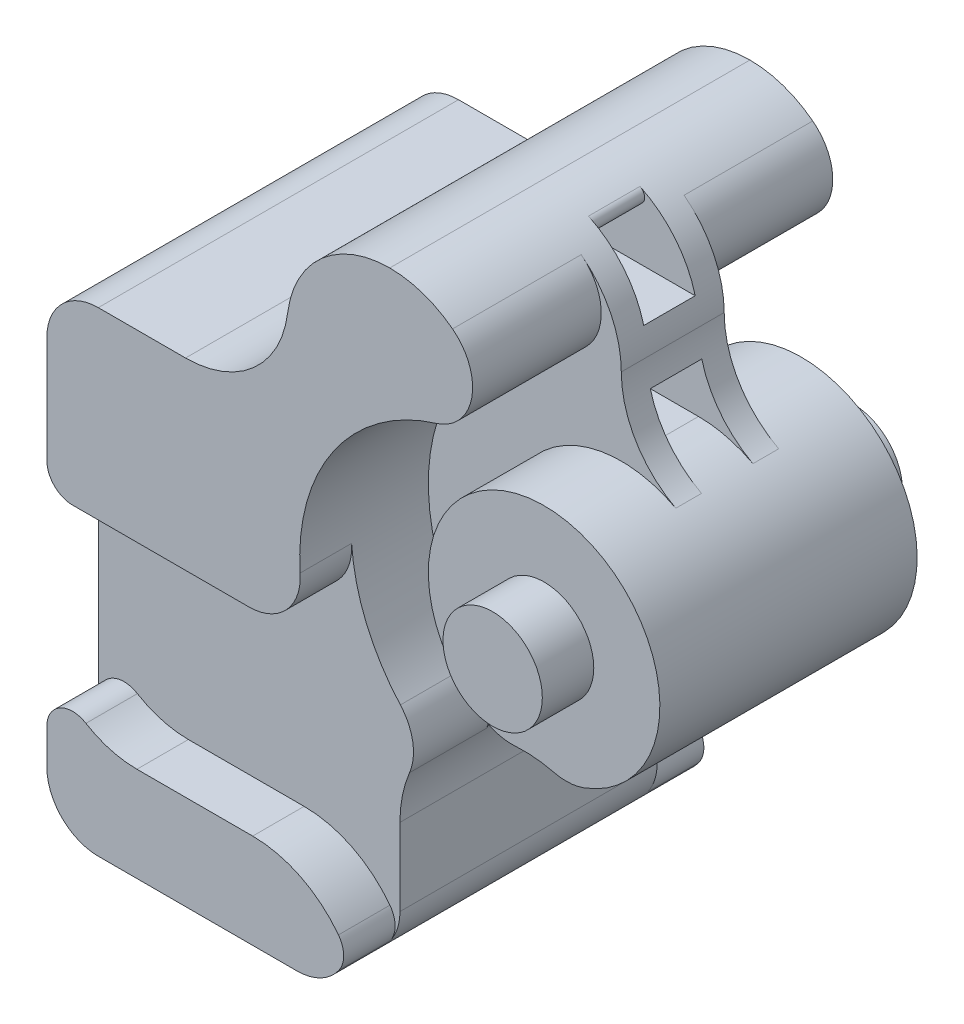
SolidWorks part; units mm, degrees
material "ABS"
ref_plane "Front Plane" through (0, 0, 0) normal (0, 0, 1) x (1, 0, 0)
ref_plane "Top Plane" through (0, 0, 0) normal (0, 1, 0) x (1, 0, 0)
ref_plane "Right Plane" through (0, 0, 0) normal (1, 0, 0) x (0, 0, -1)
sketch "Sketch1" plane through (0, 0, 0) normal (0, 0, 1) x (1, 0, 0)
  line L0 (5.5562, 0) -> (16.6687, 0)
  line L1 (0, 5.5562) -> (22.225, 5.5562)
  line L4 (22.225, 5.5562) -> (22.225, -5.5562) construction
  line L5 (0, 5.5562) -> (22.225, 5.5562) construction
  line L9 (13.1316, 0.7956) -> (22.225, 0) construction
  line L10 (22.225, 0) -> (22.225, -9.1281) construction
  line L11 (5.5562, 0) -> (0, 0)
  line L12 (0, 0) -> (0, 5.5562)
  line L13 (13.7542, 7.9121) -> (13.1316, 0.7956) construction
  circle A0 centre (0, 0) radius 5.5562 construction
  circle A1 centre (22.225, 0) radius 5.5562 construction
  circle A2 centre (22.225, -9.1281) radius 3.5719
  arc A3 (22.225, -5.5562) -> (22.225, 5.5562) centre (22.225, 0) ccw
  circle A5 centre (22.225, 0) radius 1.7859
  circle A6 centre (22.225, -9.1281) radius 1.7859
  arc A7 (16.6687, 0) -> (22.225, -5.5562) centre (22.225, 0) ccw
  circle A23 centre (22.225, 0) radius 9.1281 construction
  circle A30 centre (2.7781, 2.7781) radius 2.7781
  circle A31 centre (0.8137, 4.7426) radius 0.8137
  circle A32 centre (13.1316, 0.7956) radius 1.7859
  circle A33 centre (13.1316, 0.7956) radius 3.5719
  circle A34 centre (13.7542, 7.9121) radius 1.7859
  circle A35 centre (13.7542, 7.9121) radius 3.5719
  arc A36 (14.9108, 0.6399) -> (22.225, -7.3422) centre (22.225, 0) ccw
  arc A37 (22.225, -10.9141) -> (11.3525, 0.9512) centre (22.225, 0) cw
  arc A38 (22.225, -12.7) -> (9.5733, 1.1069) centre (22.225, 0) cw
  dimension "D1" = 22.225
  dimension "D2" = 11.1125
  dimension "D3" = 3.5719
  dimension "D5" = 7.1437
  dimension "D4" = 95
sketch "Sketch3" plane through (0, 0, 0) normal (0, 0, 1) x (1, 0, 0)
  line L0 (0.8137, 5.5562) -> (11.0694, 5.5562)
  line L1 (0, 5.5562) -> (22.225, 5.5562) construction
  line L2 (0, 5.5562) -> (0, 2.7781)
  line L3 (2.7781, 0) -> (9.6495, 0)
  line L4 (5.5562, 0) -> (16.6687, 0) construction
  line L5 (0, 2.7781) -> (0, 0)
  line L6 (0, 0) -> (2.7781, 0)
  line L7 (0, 0) -> (0, -3.175)
  line L8 (0, -3.175) -> (9.6495, -3.175)
  line L9 (9.6495, -3.175) -> (9.6495, 0)
  line L10 (0, 5.5562) -> (0.8137, 5.5562)
  line L11 (0, 5.5562) -> (0, 11.484)
  line L12 (0, 11.484) -> (13.7542, 11.484)
  line L13 (9.3057, 0.7956) -> (9.3057, -3.175)
  circle A0 centre (13.1316, 0.7956) radius 3.5719
  circle A1 centre (13.7542, 7.9121) radius 3.5719
  circle A2 centre (13.7542, 7.9121) radius 1.5319
  circle A3 centre (13.1316, 0.7956) radius 3.5719 construction
  circle A5 centre (13.7542, 7.9121) radius 3.5719 construction
  circle A6 centre (0.8137, 4.7426) radius 0.8137 construction
  circle A8 centre (2.7781, 2.7781) radius 2.7781
  circle A9 centre (13.1316, 0.7956) radius 3.8259
  arc A11 (9.5733, 1.1069) -> (9.6495, -1.7736) centre (22.225, 0) ccw
  point P40 (9.3057, -3.175)
  dimension "D2" = 3.0639
  dimension "D3" = 0.254
  dimension "D1" = 3.175
extrude "Boss-Extrude1" add sketch "Sketch3" along normal blind 7.9375 contours A8 L3 A0 A1 L0 | A1 A2 | A8 | A8 L2 | A8 | A8 | A8 L0 | A8 L5 L6 | L8 L9 L3 L6 L7 | A1 L12 L11 L10 L0 region at (5.3993, 8.5885, 0) region at (0.6205, 4.9357, 0) region at (7.663, 3.0491, 0) region at (2.7781, 2.7781, 0) region at (10.5922, 9.3443, 0) region at (0.6205, 0.6205, 0) region at (4.6529, -1.5875, 0)
extrude "Boss-Extrude2" add sketch "Sketch3<4>" along normal blind 9.525 and the other way blind 1.5875 contours A2 region at (13.7542, 7.9121, 0)
sketch "Sketch3<4>" plane through (0, 0, 0) normal (0, 0, 1) x (1, 0, 0) same geometry as "Sketch3"
sketch "Sketch7" plane through (0, 0, 7.9375) normal (0, 0, 1) x (1, 0, 0)
  line L0 (0, 5.5562) -> (11.1125, 5.5562)
  line L1 (0, 5.5562) -> (22.225, 5.5562) construction
  line L2 (0, 0) -> (9.525, 0)
  line L3 (5.5562, 0) -> (16.6687, 0) construction
  line L4 (22.225, 5.5562) -> (22.225, -5.5562) construction
  line L5 (0, 0) -> (0, -3.175)
  line L6 (0, -3.175) -> (9.3057, -3.175)
  line L9 (13.7542, 11.484) -> (0, 11.484)
  line L10 (0, 11.484) -> (0, 5.5562)
  line L13 (9.3057, 0) -> (9.3057, -3.175)
  line L14 (9.3057, 0.7956) -> (9.3057, -3.175) construction
  arc A0 (9.5733, 1.1069) -> (22.225, -12.7) centre (22.225, 0) ccw construction
  circle A1 centre (22.225, 0) radius 12.7
  circle A2 centre (13.7542, 7.9121) radius 3.5719
  circle A3 centre (13.7542, 7.9121) radius 3.5719 construction
  circle A4 centre (2.7781, 2.7781) radius 2.7781
  circle A5 centre (2.7781, 2.7781) radius 2.7781 construction
  circle A6 centre (0.8137, 4.7426) radius 0.8137
  circle A7 centre (0.8137, 4.7426) radius 0.8137 construction
  line M3 (0, 11.484) -> (0, -3.175)
  line M4 (0, -3.175) -> (9.3057, -3.175)
  line M8 (13.7542, 11.484) -> (0, 11.484)
extrude "Boss-Extrude3" add sketch "Sketch7" along normal blind 1.5875 contours A2 L0 A1 M8 M3 | A2 A1 L0 | A1 L2 M3 M4 | A6 L0 M3 | A4 L2 M3 region at (5.397, 8.5897, 7.9375) region at (0.1818, 5.3745, 7.9375) region at (0.6205, 0.6205, 7.9375) region at (10.9254, 5.623, 7.9375) region at (4.6529, -1.5875, 7.9375)
extrude "Boss-Extrude4" add sketch "Sketch7<3>" against normal blind 1.5875 from surface contours L2 M3 M4 | A2 L0 A1 M8 M3 | A6 L0 M3 | A4 L2 M3 | A2 A1 L0 region at (5.397, 8.5897, 7.9375) region at (0.1818, 5.3745, 7.9375) region at (0.6205, 0.6205, 7.9375) region at (10.9254, 5.623, 7.9375) region at (4.6529, -1.5875, 7.9375) starting at face at (8.1785, 3.9061, 0)
sketch "Sketch7<3>" plane through (0, 0, 7.9375) normal (0, 0, 1) x (1, 0, 0) same geometry as "Sketch7"
fillet "Fillet1" radius 3.5719 2 edges at (11.0694, 5.5562, -0.7937) (11.0694, 5.5562, 8.7312)
sketch "Sketch8" plane through (0, 0, 9.525) normal (0, 0, 1) x (1, 0, 0)
  line L4 (9.3057, -3.175) -> (9.3057, 0)
  line L5 (0, 2.7781) -> (0, -3.175)
  line L6 (0, -3.175) -> (9.3057, -3.175)
  line L7 (9.3057, -3.175) -> (9.3057, 0)
  line L9 (0, 2.7781) -> (0, -3.175)
  line L10 (0, -3.175) -> (9.3057, -3.175)
  line L13 (9.3057, 0) -> (2.7781, 0)
  line L14 (9.3057, 0) -> (2.7781, 0)
  circle A0 centre (6.35, -3.5719) radius 3.5719
  arc A2 (0, 2.7781) -> (2.7781, 0) centre (2.7781, 2.7781) ccw
  arc A3 (0, 2.7781) -> (2.7781, 0) centre (2.7781, 2.7781) ccw
  point P2 (6.35, 0)
  dimension "D2" = 7.1437
  dimension "D1" = 3.5719
  dimension "D3" = 0
extrude "Cut-Extrude5" cut sketch "Sketch8" against normal blind 1.5875 contours A0 region at (8.6031, -0.4448, 9.525)
extrude "Cut-Extrude6" cut sketch "Sketch8<4>" against normal blind 1.5875 from surface contours A0 region at (8.6031, -0.4448, 9.525) starting at face at (15.2862, 7.9121, 0)
sketch "Sketch8<4>" plane through (0, 0, 9.525) normal (0, 0, 1) x (1, 0, 0) same geometry as "Sketch8"
sketch "Sketch9" plane through (0, 0, 9.525) normal (0, 0, 1) x (1, 0, 0)
  line L0 (0.8137, 5.8102) -> (6.7147, 5.8102)
  line L1 (11.8492, 11.23) -> (0.254, 11.23)
  line L2 (0.254, 11.23) -> (0.254, 5.6518)
  line L3 (0.8137, 5.5562) -> (6.7147, 5.5562)
  line L4 (13.7542, 11.484) -> (0, 11.484)
  line L5 (0, 11.484) -> (0, 4.7426)
  line L6 (0.8137, 5.5562) -> (6.7147, 5.5562)
  line L7 (13.7542, 11.484) -> (0, 11.484)
  line L8 (0, 11.484) -> (0, 4.7426)
  line L9 (9.0517, -2.921) -> (9.0517, -1.646)
  line L10 (9.3057, -3.175) -> (9.3057, -1.5664)
  line L11 (6.35, 0) -> (2.7781, 0)
  line L12 (0, 2.7781) -> (0, -3.175)
  line L13 (0, -3.175) -> (9.3057, -3.175)
  line L16 (0, 2.7781) -> (0, -3.175)
  line L17 (0, -3.175) -> (9.3057, -3.175)
  line L18 (6.35, -0.254) -> (2.7781, -0.254)
  line L19 (0.254, 1.0981) -> (0.254, -2.921)
  line L20 (0.254, -2.921) -> (9.0517, -2.921)
  line L25 (6.35, 0) -> (2.7781, 0) construction
  line L26 (6.35, 0) -> (2.7781, 0)
  line L27 (9.3057, -3.175) -> (9.3057, -1.5664) construction
  line L28 (9.3057, -3.175) -> (9.3057, -1.5664)
  arc A0 (6.7147, 5.8102) -> (9.051, 11.484) centre (6.7147, 9.1281) ccw
  arc A1 (12.3835, 11.484) -> (9.9842, 8.5634) centre (13.7542, 7.9121) ccw
  arc A2 (9.3057, -1.5664) -> (6.35, 0) centre (6.35, -3.5719) ccw
  arc A3 (6.7147, 5.5562) -> (10.2345, 8.5201) centre (6.7147, 9.1281) ccw
  arc A4 (13.7542, 11.484) -> (10.2345, 8.5201) centre (13.7542, 7.9121) ccw
  arc A5 (0.8137, 5.5562) -> (0, 4.7426) centre (0.8137, 4.7426) ccw
  arc A6 (6.7147, 5.5562) -> (10.2345, 8.5201) centre (6.7147, 9.1281) ccw
  arc A7 (13.7542, 11.484) -> (10.2345, 8.5201) centre (13.7542, 7.9121) ccw
  arc A8 (0.8137, 5.5562) -> (0, 4.7426) centre (0.8137, 4.7426) ccw
  arc A9 (0, 2.7781) -> (2.7781, 0) centre (2.7781, 2.7781) ccw
  arc A10 (9.3057, -1.5664) -> (6.35, 0) centre (6.35, -3.5719) ccw
  arc A11 (0, 2.7781) -> (2.7781, 0) centre (2.7781, 2.7781) ccw
  arc A12 (0.8137, 5.8102) -> (0, 5.4338) centre (0.8137, 4.7426) ccw
  arc A13 (9.6441, -3.175) -> (6.35, -0.254) centre (6.35, -3.5719) ccw
  arc A14 (0, 1.5633) -> (2.7781, -0.254) centre (2.7781, 2.7781) ccw
  arc A15 (0.8137, 5.8102) -> (0.254, 5.6518) centre (0.8137, 4.7426) ccw construction
  arc A16 (6.7147, 5.8102) -> (9.9842, 8.5634) centre (6.7147, 9.1281) ccw construction
  arc A17 (0.254, 1.0981) -> (2.7781, -0.254) centre (2.7781, 2.7781) ccw construction
  arc A18 (9.0517, -1.646) -> (6.35, -0.254) centre (6.35, -3.5719) ccw construction
  arc A19 (11.8492, 11.23) -> (9.9842, 8.5634) centre (13.7542, 7.9121) ccw construction
  line M19 (0.8137, 5.5562) -> (6.7147, 5.5562)
  arc M20 (6.7147, 5.5562) -> (10.2345, 8.5201) centre (6.7147, 9.1281) ccw
  arc M21 (10.2345, 8.5201) -> (13.7542, 11.484) centre (13.7542, 7.9121) cw
  line M22 (13.7542, 11.484) -> (0, 11.484)
  arc M24 (0, 4.7426) -> (0.8137, 5.5562) centre (0.8137, 4.7426) cw
  dimension "D1" = 0
  dimension "D2" = 0
  dimension "D3" = 0.254
  dimension "D4" = 0.254
extrude "Cut-Extrude7" cut sketch "Sketch9" against normal blind 1.5875 contours L0 A12 L8 A0 M24 M19 M20 M21 M22 | L16 A14 L18 A13 L17 A10 A11 region at (3.7642, 5.6571, 9.525) region at (4.5043, -0.0587, 9.525)
extrude "Cut-Extrude8" cut sketch "Sketch9<3>" against normal blind 1.5875 from surface contours L16 A14 L18 A13 L17 A10 A11 | L0 A12 L8 A0 M24 M19 M20 M21 M22 region at (3.7642, 5.6571, 9.525) region at (4.5043, -0.0587, 9.525) starting at face at (15.2862, 7.9121, 0)
sketch "Sketch9<3>" plane through (0, 0, 9.525) normal (0, 0, 1) x (1, 0, 0) same geometry as "Sketch9"
fillet "Fillet3" radius 1.5875 3 edges at (0, -3.175, 3.9688) (0, 11.484, 3.9688) (9.3057, -3.175, 3.9688)
fillet "Fillet2" radius 0.7937 8 edges at (0, 5.4338, -0.7937) (0, 1.5633, -0.7937) (0, 1.5633, 8.7312) (0, 5.4338, 8.7312) (12.3835, 11.484, 8.7312) (12.3835, 11.484, -0.7937) (9.2579, -1.9743, -0.7938) (9.2579, -1.9743, 8.7312)
sketch "Sketch10" plane through (0, 0, 9.525) normal (0, 0, 1) x (1, 0, 0)
  line L0 (13.7542, 11.484) -> (10.0633, 11.484)
  circle A0 centre (13.7542, 7.9121) radius 3.5719
  circle A1 centre (13.7542, 7.9121) radius 5.9531
  arc A2 (14.411, 4.4012) -> (13.7542, 11.484) centre (13.7542, 7.9121) ccw construction
  arc A3 (16.4914, 2.6256) -> (10.1406, 3.1812) centre (13.1316, 0.7956) ccw
  arc A4 (14.411, 4.4012) -> (9.3057, 0.7956) centre (13.1316, 0.7956) ccw construction
  line M3 (10.0633, 11.484) -> (1.5875, 11.484)
  arc M9 (6.7147, 5.8102) -> (9.9842, 8.5634) centre (6.7147, 9.1281) ccw
  arc M10 (9.9842, 8.5634) -> (10.6975, 10.2129) centre (13.7542, 7.9121) cw
  arc M11 (10.6975, 10.2129) -> (10.0633, 11.484) centre (10.0633, 10.6903) ccw
  dimension "D1" = 2.3812
extrude "Cut-Extrude9" cut sketch "Sketch10" against normal blind 3.9688 contours A3 A0 L0 A1 M11 M10 M9 | A1 M3 M9 M10 M11 region at (10.1692, 6.3249, 9.525) region at (9.1229, 9.1272, 9.525)
extrude "Cut-Extrude10" cut sketch "Sketch10<3>" along normal blind 3.9688 from surface contours A1 M3 M9 M10 M11 | A3 A0 L0 A1 M11 M10 M9 region at (10.1692, 6.3249, 9.525) region at (9.1229, 9.1272, 9.525) starting at face at (4.5518, 8.3865, -1.5875)
sketch "Sketch10<3>" plane through (0, 0, 9.525) normal (0, 0, 1) x (1, 0, 0) same geometry as "Sketch10"
fillet "Fillet4" radius 1.5875 6 edges at (8.082, 6.1051, -0.7937) (10.1406, 3.1812, 1.1906) (8.082, 6.1051, 8.7312) (10.1406, 3.1812, 6.7469) (8.9917, 11.484, 0.3969) (8.9917, 11.484, 7.5406)
fillet "Fillet5" radius 1.5875 3 edges at (12.4977, 4.5686, 1.1906) (14.411, 4.4012, 3.9688) (12.4977, 4.5686, 6.7469)
sketch "Sketch11" plane through (0, 11.484, 0) normal (0, 1, 0) x (1, 0, 0)
  line L0 (13.7542, -5.5563) -> (6.4794, -5.5563) construction
  line L1 (13.7542, -2.3813) -> (7.4042, -2.3813)
  line L2 (13.7542, -2.3813) -> (13.7542, -5.5563)
  line L3 (13.7542, -5.5563) -> (7.4042, -5.5563)
  line L4 (7.4042, -2.3813) -> (7.4042, -5.5563)
  dimension "D1" = 6.35
extrude "Boss-Extrude5" add sketch "Sketch11" along normal blind 5.5562
sketch "Sketch12" plane through (0, 0, -1.5875) normal (0, 0, -1) x (-1, 0, 0)
  line L4 (-6.4794, 11.484) -> (-7.4042, 11.484)
  line L5 (-7.4042, 11.484) -> (-7.4042, 17.0403)
  line L6 (-7.4042, 17.0403) -> (-13.7542, 17.0403)
  line L7 (-13.7542, 17.0403) -> (-13.7542, 11.484)
  line L8 (-6.4794, 11.484) -> (-7.4042, 11.484)
  line L9 (-7.4042, 11.484) -> (-7.4042, 17.0403)
  line L10 (-7.4042, 17.0403) -> (-13.7542, 17.0403)
  line L11 (-13.7542, 17.0403) -> (-13.7542, 11.484)
  circle A0 centre (-13.7542, 7.9121) radius 3.5719
  circle A1 centre (-13.7542, 7.9121) radius 5.9531
  arc A2 (-9.3192, 3.941) -> (-7.815, 7.506) centre (-13.7542, 7.9121) ccw construction
  arc A3 (-11.9608, 4.8231) -> (-14.984, 4.5586) centre (-13.7542, 7.9121) ccw construction
  arc A10 (-9.3192, 3.941) -> (-8.0109, 9.4787) centre (-13.7542, 7.9121) ccw
  arc A11 (-6.4794, 11.484) -> (-8.0109, 9.4787) centre (-6.4794, 9.8965) ccw
  arc A12 (-11.9608, 4.8231) -> (-13.7542, 11.484) centre (-13.7542, 7.9121) ccw
  arc A13 (-12.8675, 4.6123) -> (-11.9608, 4.8231) centre (-12.7579, 6.196) ccw
  arc A14 (-9.6013, 2.2702) -> (-12.8675, 4.6123) centre (-13.1316, 0.7956) ccw
  arc A15 (-9.3192, 3.941) -> (-9.6013, 2.2702) centre (-8.1365, 2.882) ccw
  arc A16 (-9.3192, 3.941) -> (-8.0109, 9.4787) centre (-13.7542, 7.9121) ccw
  arc A17 (-6.4794, 11.484) -> (-8.0109, 9.4787) centre (-6.4794, 9.8965) ccw
  arc A18 (-11.9608, 4.8231) -> (-13.7542, 11.484) centre (-13.7542, 7.9121) ccw
  arc A19 (-12.8675, 4.6123) -> (-11.9608, 4.8231) centre (-12.7579, 6.196) ccw
  arc A20 (-9.6013, 2.2702) -> (-12.8675, 4.6123) centre (-13.1316, 0.7956) ccw
  arc A21 (-9.3192, 3.941) -> (-9.6013, 2.2702) centre (-8.1365, 2.882) ccw
  dimension "D1" = 0
extrude "Boss-Extrude7" add sketch "Sketch12" against normal up to surface (11.1125 mm away) contours A17 L8 L9 L10 L11 A1 region at (10.1007, 14.6192, -1.5875) up to face at (15.2862, 7.9121, 9.525)
sketch "Sketch13" plane through (0, 0, 5.5563) normal (0, 0, 1) x (1, 0, 0)
  line L0 (13.7542, 13.8653) -> (13.7542, 11.484) construction
  line L1 (13.7542, 11.484) -> (10.5792, 11.484)
  line L2 (13.7542, 11.484) -> (13.7542, 13.0715)
  line L3 (13.7542, 13.0715) -> (10.5792, 13.0715)
  line L4 (10.5792, 11.484) -> (10.5792, 13.0715)
  line L5 (13.7542, 16.2465) -> (10.5792, 16.2465)
  line L6 (13.7542, 16.2465) -> (13.7542, 14.659)
  line L7 (13.7542, 14.659) -> (10.5792, 14.659)
  line L8 (10.5792, 16.2465) -> (10.5792, 14.659)
  line L9 (10.5792, 14.659) -> (10.5792, 13.0715) construction
  line L10 (13.7542, 14.659) -> (13.7542, 13.0715) construction
  arc A0 (10.5792, 14.659) -> (10.5792, 13.0715) centre (10.5792, 13.8653) ccw
  arc A1 (10.5792, 16.2465) -> (10.5792, 11.484) centre (10.5792, 13.8653) ccw
  line M11 (13.7542, 11.484) -> (13.7542, 13.8653)
  arc M12 (13.7542, 13.8653) -> (9.3192, 3.941) centre (13.7542, 7.9121) ccw
  dimension "D1" = 1.5875
  dimension "D2" = 1.5875
  dimension "D3" = 3.175
extrude "Cut-Extrude11" cut sketch "Sketch13" against normal blind 1.5875 from offset 0.7937 contours L4 L1 L3 M11 M12 | A1 L4 M12 | L5 L8 L7 L6 | L8 A1 L4 A0 M12 | L4 L3 M12 region at (12.1705, 12.2759, 5.5563) region at (10.1202, 12.0806, 5.5563) region at (9.3828, 14.1505, 5.5563) region at (10.6471, 13.0306, 5.5563) region at (12.1667, 15.4528, 5.5563) offset against normal yes
fillet "Fillet6" radius 3.175 1 edges at (7.4042, 17.0403, 3.9688)
fillet "Fillet8" radius 3.175 3 edges at (13.7542, 17.0403, 3.9688) (13.7542, 11.484, 5.1594) (7.4042, 11.484, 3.9688)
fillet "Fillet9" radius 0.254 1 edges at (12.6793, 16.2465, 3.9688)
fillet "Fillet10" radius 1.5875 2 edges at (13.7542, 13.8653, 0.3969) (13.7542, 13.8653, 7.5406)
